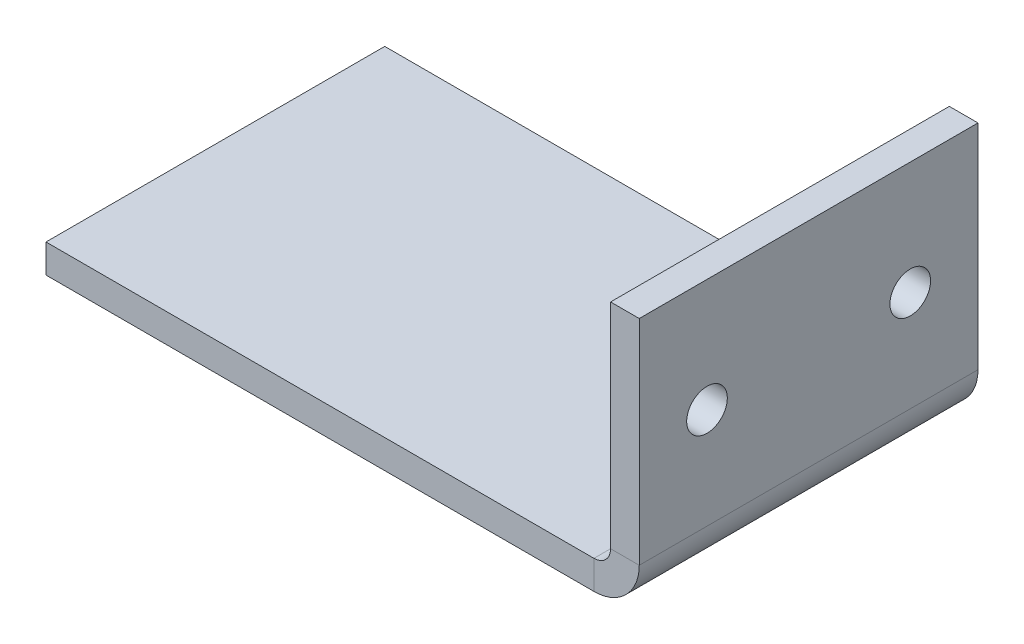
SolidWorks part; units mm, degrees
note: The reader was unsure of these and kept them because the rebuilt part matched: flange length of "Edge-Flange1".
ref_plane "Front Plane" through (0, 0, 0) normal (0, 0, 1) x (1, 0, 0)
ref_plane "Top Plane" through (0, 0, 0) normal (0, 1, 0) x (1, 0, 0)
ref_plane "Right Plane" through (0, 0, 0) normal (1, 0, 0) x (0, 0, -1)
sketch "Sketch1" plane through (0, 0, 0) normal (0, 1, 0) x (1, 0, 0)
  line L1 (-12.5, 7.5) -> (12.5, 7.5)
  line L2 (-12.5, 7.5) -> (-12.5, -7.5)
  line L3 (-12.5, -7.5) -> (12.5, -7.5)
  line L4 (12.5, 7.5) -> (12.5, -7.5)
  line L5 (-12.5, 7.5) -> (12.5, -7.5) construction
  line L6 (-12.5, -7.5) -> (12.5, 7.5) construction
  point P0 (0, 0)
  dimension "D1" = 15
  dimension "D2" = 25
base flange "Base-Flange1" sketch "Sketch1" thickness 1.27 reverse thickness direction no parameters "D1"=0.7366
edge flange "Edge-Flange1" sketch "Sketch8" flange angle 90 flange length 10.2 flange position material outside bend radius 0.7366 thickness 1.27 relief rectangular parameters "D6"=10
sketch "Sketch8" plane through (12.5, 0, 0) normal (1, 0, 0) x (0, 0, -1)
  line L2 (-7.5, 0) -> (-7.5, 10.2)
  line L3 (-7.5, 10.2) -> (7.5, 10.2)
  line L4 (7.5, 10.2) -> (7.5, 0)
  line L7 (-7.5, 0) -> (7.5, 0) construction
  line L8 (-7.5, 0) -> (7.5, 0)
bend "EdgeBend1" bend radius 0.7366 bend angle 90 parameters "D5"=1
sketch "Sketch9" plane through (0, 0, 0) normal (0, 1, 0) x (1, 0, 0)
  line L0 (-12.5, -7.5) -> (11.7634, -7.5) construction
  line L1 (-11, 6) -> (11, 6) construction
  line L2 (-11, 6) -> (-11, -6) construction
  line L3 (-11, -6) -> (11, -6) construction
  line L4 (11, 6) -> (11, -6) construction
  line L5 (-11, 6) -> (11, -6) construction
  line L6 (-11, -6) -> (11, 6) construction
  line L7 (-12.5, 7.5) -> (-12.5, -7.5) construction
  point P0 (0, 0)
  dimension "D1" = 1.5
  dimension "D2" = 1.5
sketch "Sketch10" plane through (13.77, 0, 0) normal (1, 0, 0) x (0, 0, -1)
  line L0 (-4.5, 5.2) -> (4.5, 5.2) construction
  line L2 (7.5, 10.2) -> (-7.5, 10.2) construction
  line L3 (0, 6.3085) -> (0, -6.3085) construction
  point P3 (0, 5.2)
  dimension "D1" = 5
  dimension "D2" = 9
hole_wizard "M1.6 Clearance Hole1" positions "3DSketch1" profile "Sketch11" hole size "M1.6" standard "ANSI Metric" end condition through all
sketch3d "3DSketch1"
  point P0 (13.77, 5.2, 4.5)
  point P3 (13.77, 5.2, -4.5)
sketch "Sketch11" plane through (13.77, 5.2, 4.5) normal (0, 1, 0) x (0, 0, -1)
  line L0 (0, 0) -> (0, 26.27)
  line L1 (0, 26.27) -> (0.9, 26.27)
  line L2 (0.9, 26.27) -> (0.9, 0)
  line L5 (0.9, 0) -> (0, 0)
  line L11 (0, -6.35) -> (0, 107.95) construction
  dimension "Thru Hole Dia." = 1.8
  dimension "Thru Hole Depth" = 26.27
sketch "Bend-Lines1" [suppressed] plane through (0, 0, 0) normal (0, 1, 0) x (1, 0, 0)
sketch "Bounding-Box1" [suppressed] plane through (0, 0, 0) normal (0, 1, 0) x (1, 0, 0)
sheet metal parameters "Sheet-Metal1" thickness 1.27 parameters "D1"=0.7366
flat pattern "Flat-Pattern1" [suppressed]
sketch "Bend-Lines2" plane through (0, 0, 0) normal (0, 1, 0) x (1, 0, 0)
sketch3d "Bounding-Box2" [suppressed]
  line L0 (-12.5, -6, 0) -> (12.5, -6, 0) construction
  line L1 (-12.5, 6, 0) -> (12.5, 6, 0) construction
  line L2 (-12.5, -6, 0) -> (-12.5, 6, 0) construction
  line L3 (12.5, -6, 0) -> (12.5, 6, 0) construction
sheet metal parameters "Sheet-Metal2" thickness 1.27 parameters "D1"=0.7366
flat pattern "Flat-Pattern1"
sketch "Bend-Lines2" plane through (0, 0, 0) normal (0, 1, 0) x (1, 0, 0)
  line L0 (12.7409, -7.5) -> (12.7409, 7.5) construction
  line L1 (12.7409, -7.5) -> (12.7409, 7.5) construction
sketch3d "Bounding-Box2" [suppressed]
  line L0 (23.1818, -7.5, 0) -> (-12.5, -7.5, 0) construction
  line L1 (23.1818, 7.5, 0) -> (-12.5, 7.5, 0) construction
  line L2 (23.1818, -7.5, 0) -> (23.1818, 7.5, 0) construction
  line L3 (-12.5, -7.5, 0) -> (-12.5, 7.5, 0) construction
bend of the flat pattern "Flatten-<EdgeBend1>1"
sheet metal parameters "Sheet-Metal3" thickness 1.27 parameters "D1"=0.7366
flat pattern "Flat-Pattern1" [suppressed]
sketch "Bend-Lines2" plane through (0, 0, 0) normal (0, 1, 0) x (1, 0, 0)
  line L0 (12.7409, -7.5) -> (12.7409, 7.5) construction
  line L1 (12.7409, -7.5) -> (12.7409, 7.5) construction
sketch3d "Bounding-Box2" [suppressed]
  line L0 (23.1818, -7.5, 0) -> (-12.5, -7.5, 0) construction
  line L1 (23.1818, 7.5, 0) -> (-12.5, 7.5, 0) construction
  line L2 (23.1818, -7.5, 0) -> (23.1818, 7.5, 0) construction
  line L3 (-12.5, -7.5, 0) -> (-12.5, 7.5, 0) construction
bend of the flat pattern "Flatten-<EdgeBend1>1"
sketch "Sketch10-1" [suppressed] plane through (12.9818, -1.27, 0) normal (0, -1, 0) x (0, 0, -1)
  line L0 (-4.5, 5.2) -> (4.5, 5.2) construction
  line L2 (7.5, 10.2) -> (-7.5, 10.2) construction
  point P3 (0, 5.2)
  dimension "D1" = 5
  dimension "D2" = 9
